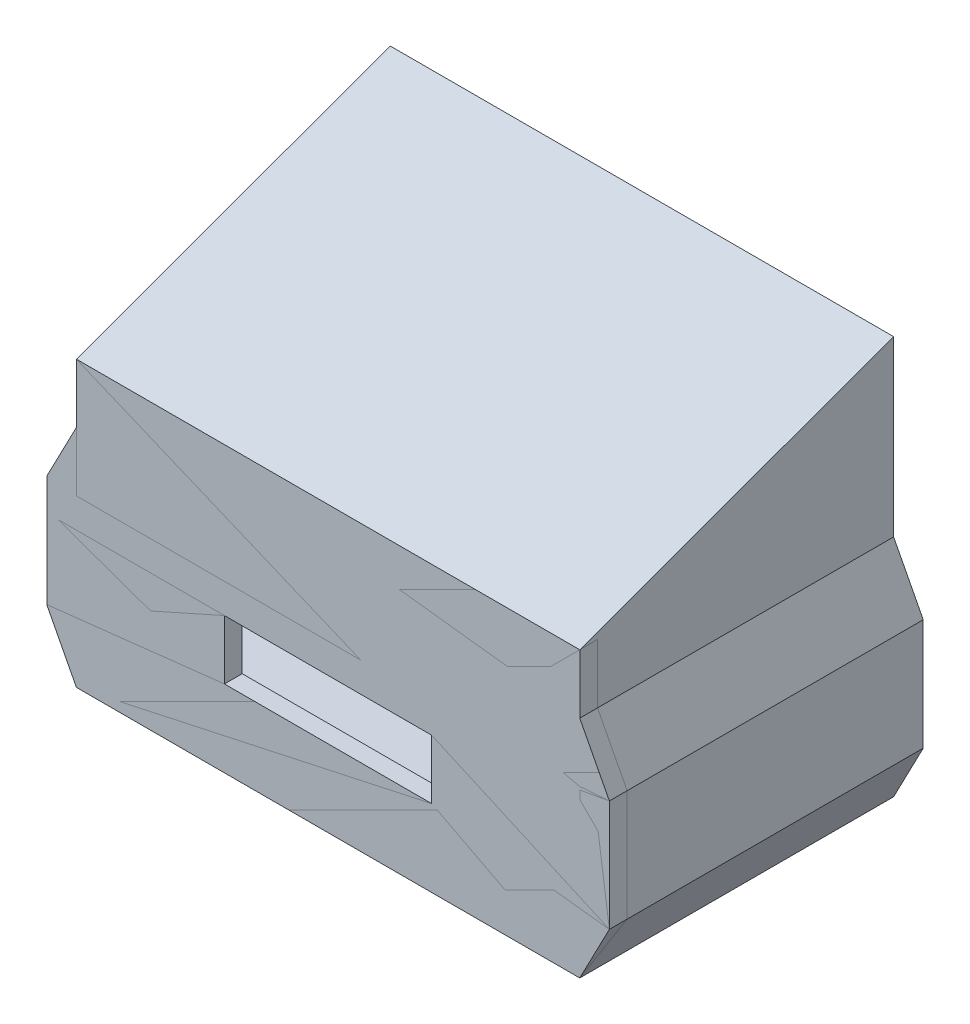
SolidWorks part; units mm, degrees
ref_plane "Front Plane" through (0, 0, 0) normal (0, 0, 1) x (1, 0, 0)
ref_plane "Top Plane" through (0, 0, 0) normal (0, 1, 0) x (1, 0, 0)
ref_plane "Right Plane" through (0, 0, 0) normal (1, 0, 0) x (0, 0, -1)
sketch "Sketch1" plane through (0, 0, 0) normal (0, 1, 0) x (1, 0, 0)
  line L1 (0, 0) -> (85, 0)
  line L2 (0, 0) -> (0, 93)
  line L3 (0, 93) -> (85, 93)
  line L4 (85, 0) -> (85, 93)
  dimension "D1" = 85
  dimension "D2" = 93
extrude "Boss-Extrude1 (Base)" add sketch "Sketch1" along normal blind 3
sketch "Sketch4" plane through (0, 0, 0) normal (0, 0, 1) x (1, 0, 0)
  line L0 (-3.1, 23) -> (0, 26.1)
  line L1 (0, 26.1) -> (0, 23)
  line L2 (0, 23) -> (-3.1, 23)
  line L3 (0, 3) -> (85, 3) construction
  line L6 (0, 3) -> (0, 0) construction
  line L7 (42.5, 28.9013) -> (42.5, -8.4397) construction
  line L8 (85, 3) -> (85, 0) construction
  line L9 (85, 23) -> (88.1, 23)
  line L10 (85, 26.1) -> (85, 23)
  line L11 (88.1, 23) -> (85, 26.1)
  dimension "D1" = 20
  dimension "D2" = 3.1
  dimension "D3" = 3.1
  dimension "D4" = 42.5
sketch "Sketch5" plane through (0, 0, 0) normal (0, 0, 1) x (1, 0, 0)
  line L6 (42.5, 3) -> (42.5, 26.9028) construction
  line L11 (-5, 28.3909) -> (0, 38)
  line L12 (0, 38) -> (0, 0)
  line L13 (0, 0) -> (-5, 9.6091)
  line L14 (-5, 9.6091) -> (-5, 28.3909)
  line L15 (90, 9.6091) -> (90, 28.3909)
  line L16 (0, 3) -> (85, 3) construction
  line L21 (85, 0) -> (90, 9.6091)
  line L22 (85, 38) -> (85, 0)
  line L23 (90, 28.3909) -> (85, 38)
  dimension "D1" = 5
  dimension "D2" = 35
extrude "Boss-Extrude4 (Side Walls)" add sketch "Sketch5" against normal through all
extrude "Cut-Extrude2 (Guide Holes)" cut sketch "Sketch4" against normal through all from offset 3
sketch "Sketch15" plane through (0, 0, 0) normal (0, 0, 1) x (1, 0, 0)
  line L0 (85, 23) -> (85, 3) construction
  line L1 (0, 23) -> (85, 23)
  line L2 (0, 23) -> (0, 3)
  line L3 (0, 3) -> (85, 3)
  line L4 (85, 23) -> (85, 3)
extrude "Boss-Extrude9 (Rear Wall)" add sketch "Sketch15" against normal blind 3
sketch "Sketch17" plane through (0, 23, 0) normal (0, 1, 0) x (1, 0, 0)
  line L1 (85, 3) -> (0, 3)
  line L2 (85, 3) -> (85, 0)
  line L3 (85, 0) -> (0, 0)
  line L4 (0, 3) -> (0, 0)
extrude "Boss-Extrude1 (Rear Wall)" add sketch "Sketch17" along normal blind 12 from offset 3
sketch "Sketch30" plane through (0, 0, 0) normal (0, 0, 1) x (1, 0, 0)
  line L1 (0, 26) -> (85, 26)
  line L2 (0, 26) -> (0, 28)
  line L3 (0, 28) -> (85, 28)
  line L4 (85, 26) -> (85, 28)
  dimension "D1" = 2
extrude "Cut-Extrude1 (Rear Wall)" cut sketch "Sketch30" against normal blind 10
sketch "Sketch20" plane through (0, 3, 0) normal (0, 1, 0) x (1, 0, 0)
  line L0 (85, 93) -> (0, 93) construction
  line L1 (0, 3) -> (3, 3)
  line L2 (0, 3) -> (0, 93)
  line L3 (0, 93) -> (3, 93)
  line L4 (3, 3) -> (3, 93)
  line L5 (42.5, 93) -> (42.5, 70.8429) construction
  line L6 (85, 3) -> (0, 3) construction
  line L7 (0, 3) -> (0, 0) construction
  line L8 (82, 3) -> (82, 93)
  line L9 (85, 93) -> (82, 93)
  line L10 (85, 3) -> (85, 93)
  line L11 (85, 3) -> (82, 3)
  dimension "D1" = 3
extrude "Boss-Extrude2 (Side Wall)" add sketch "Sketch20" along normal blind 10 from offset 25
chamfer "Chamfer1 (Side Wall)" distance 3 angle 45 2 edges at (82, 28, -48) (3, 28, -48)
sketch "Sketch26" plane through (0, 38, 0) normal (0, 1, 0) x (1, 0, 0)
  line L3 (0, 0) -> (0, 93)
  line L4 (0, 93) -> (0, 0) construction
  line L5 (0, 93) -> (3, 93)
  line L6 (3, 93) -> (0, 93) construction
  line L7 (3, 93) -> (3, 3)
  line L12 (3, 3) -> (82, 3)
  line L13 (82, 3) -> (82, 93)
  line L14 (82, 93) -> (85, 93)
  line L15 (85, 93) -> (85, 0)
  line L16 (85, 0) -> (0, 0)
extrude "Boss-Extrude5 (Side Wall)" add sketch "Sketch26" along normal blind 50
chamfer "Chamfer2 (Roof)" distance 40 angle 70 1 edges at (42.5, 88, 0) first distance on face at (42.5, 25.7, 0)
sketch "Sketch28" plane through (0, 42.3851, 15.4269) normal (0, 0.9397, 0.342) x (1, 0, 0)
  line L1 (85, 115.3855) -> (0, 115.3855)
  line L2 (85, 115.3855) -> (85, 12.9968)
  line L3 (85, 12.9968) -> (0, 12.9968)
  line L4 (0, 115.3855) -> (0, 12.9968)
extrude "Boss-Extrude7 (Roof)" add sketch "Sketch28" against normal blind 2.5
sketch "Sketch29" plane through (90, 0, 0) normal (1, 0, 0) x (0, 0, -1)
  line L1 (93, 0) -> (98.083, 0)
  line L2 (93, 0) -> (93, 88.7054)
  line L3 (93, 88.7054) -> (98.083, 88.7054)
  line L4 (98.083, 0) -> (98.083, 88.7054)
  line L5 (0, 0) -> (-8.2889, 0)
  line L6 (0, 0) -> (0, 87.4547)
  line L7 (0, 87.4547) -> (-8.2889, 87.4547)
  line L8 (-8.2889, 0) -> (-8.2889, 87.4547)
extrude "Cut-Extrude1 (Clean up)" cut sketch "Sketch29" against normal through all
sketch "Sketch31" plane through (0, 0, 0) normal (0, -1, 0) x (1, 0, 0)
  line L0 (90, -93) -> (90, 0) construction
  line L1 (-5, -93) -> (90, -93)
  line L2 (-5, -93) -> (-5, -53)
  line L3 (-5, -53) -> (90, -53)
  line L4 (90, -93) -> (90, -53)
  line L5 (0, 0) -> (85, 0) construction
  dimension "D1" = 53
extrude "Cut-Extrude2 (Clean Up)" cut sketch "Sketch31" against normal through all
sketch "Sketch33" plane through (0, 0, 0) normal (0, 0, 1) x (1, 0, 0)
  line L5 (0, 38) -> (0, 48)
  line L15 (0, 48) -> (85, 48)
  line L16 (85, 48) -> (85, 38)
  line L17 (85, 38) -> (90, 28.3909)
  line L18 (90, 28.3909) -> (90, 9.6091)
  line L19 (90, 9.6091) -> (85, 0)
  line L20 (85, 0) -> (0, 0)
  line L21 (0, 0) -> (-5, 9.6091)
  line L22 (-5, 9.6091) -> (-5, 28.3909)
  line L23 (-5, 28.3909) -> (0, 38)
extrude "Boss-Extrude1" add sketch "Sketch33" against normal blind 3 separate body
sketch "Sketch34" plane through (0, 0, 0) normal (0, 0, 1) x (1, 0, 0)
  line L0 (85, 23) -> (0, 23) construction
  line L3 (25, 23) -> (60, 23)
  line L4 (25, 23) -> (25, 13)
  line L5 (25, 13) -> (60, 13)
  line L6 (60, 23) -> (60, 13)
  line L7 (85, 3) -> (85, 23) construction
  dimension "D1" = 25
  dimension "D2" = 10
  dimension "D3" = 35
extrude "Cut-Extrude1" cut sketch "Sketch34" against normal blind 10
